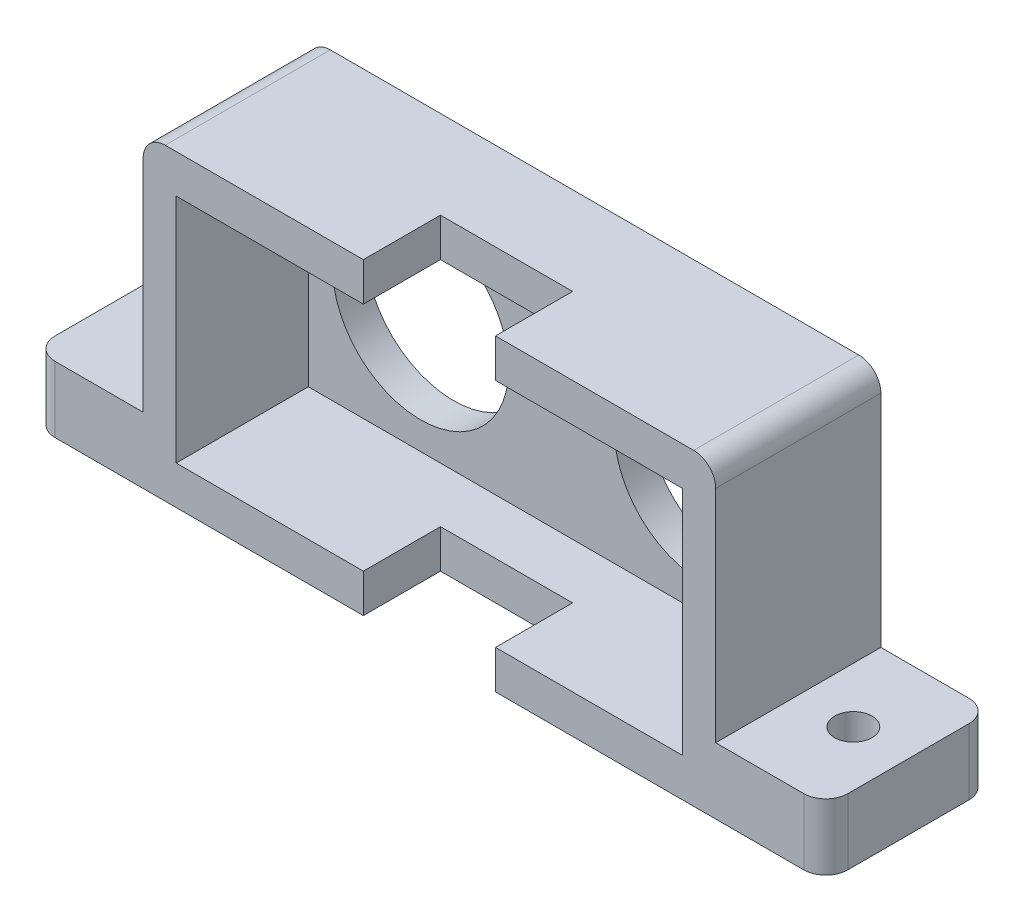
SolidWorks part; units mm, degrees
ref_plane "Plan de face" through (0, 0, 0) normal (0, 0, 1) x (1, 0, 0)
ref_plane "Plan de dessus" through (0, 0, 0) normal (0, 1, 0) x (1, 0, 0)
ref_plane "Plan de droite" through (0, 0, 0) normal (1, 0, 0) x (0, 0, -1)
sketch "Esquisse1" plane through (0, 0, 0) normal (0, 0, 1) x (1, 0, 0)
  line L0 (36, 0) -> (-36, 0)
  line L1 (-36, 0) -> (36, 0) construction
  line L2 (-36, 0) -> (-36, 28) construction
  line L3 (-36, 28) -> (36, 28) construction
  line L4 (36, 0) -> (36, 28) construction
  line L5 (-36, 0) -> (-36, 6)
  line L6 (-36, 6) -> (-26, 6)
  line L7 (-26, 6) -> (-26, 28)
  line L8 (-26, 28) -> (26, 28)
  line L9 (26, 28) -> (26, 6)
  line L10 (26, 6) -> (36, 6)
  line L11 (36, 6) -> (36, 0)
  point P4 (0, 0)
  dimension "D1" = 72
  dimension "D2" = 28
  dimension "D3" = 10
  dimension "D4" = 6
  dimension "D5" = 6
  dimension "D6" = 10
extrude "Boss.-Extru.1" add sketch "Esquisse1" along normal blind 15
sketch "Esquisse2" plane through (0, 0, 15) normal (0, 0, 1) x (1, 0, 0)
  line L0 (0, 0) -> (0, 28) construction
  line L1 (-23, 24.5) -> (23, 24.5) construction
  line L2 (-23, 24.5) -> (-23, 3.5) construction
  line L3 (-23, 3.5) -> (23, 3.5) construction
  line L4 (23, 24.5) -> (23, 3.5) construction
  line L5 (26, 28) -> (-26, 28) construction
  line L6 (-23, 14) -> (23, 14) construction
  line L9 (-23, 24.5) -> (23, 24.5)
  line L10 (-23, 24.5) -> (-23, 3.5)
  line L11 (-23, 3.5) -> (23, 3.5)
  line L12 (23, 24.5) -> (23, 3.5)
  point P4 (0, 3.5)
  point P9 (0, 14)
  dimension "D1" = 46
  dimension "D2" = 21
extrude "Enlèv. mat.-Extru.1" cut sketch "Esquisse2" against normal offset from surface (12 mm away) 3 up to face at (0, 10, 0)
sketch "Esquisse4" plane through (0, 0, 3) normal (0, 0, 1) x (1, 0, 0)
  line L0 (-4.8, 14) -> (4.8, 14) construction
  line L1 (0, 0) -> (0, 28) construction
  line L2 (-36, 0) -> (36, 0) construction
  line L3 (26, 28) -> (-26, 28) construction
  circle A0 centre (-12.8, 14) radius 8
  circle A1 centre (12.8, 14) radius 8
  point P12 (0, 14)
  point P13 (0, 14)
  dimension "D1" = 16
  dimension "D2" = 16
  dimension "D3" = 9.6
extrude "Enlèv. mat.-Extru.2" cut sketch "Esquisse4" against normal blind 3
sketch "Esquisse5" plane through (0, 0, 0) normal (0, -1, 0) x (1, 0, 0)
  line L0 (-36, 15) -> (36, 15) construction
  line L1 (-6, 15) -> (6, 15)
  line L2 (-6, 15) -> (-6, 8)
  line L3 (-6, 8) -> (6, 8)
  line L4 (6, 15) -> (6, 8)
  line L5 (0, 0) -> (0, 15) construction
  point P9 (0, 15)
  dimension "D1" = 12
  dimension "D2" = 7
extrude "Enlèv. mat.-Extru.3" cut sketch "Esquisse5" against normal up to surface (28 mm away) up to face at (0, 28, 7.5)
fillet "Congé1" radius 2 6 edges at (-36, 3, 0) (36, 3, 0) (36, 3, 15) (-36, 3, 15) (-26, 28, 7.5) (26, 28, 7.5)
sketch "Esquisse6" plane through (0, 6, 0) normal (0, 1, 0) x (1, 0, 0)
  line L0 (-36, -7.5) -> (36, -7.5) construction
  line L1 (-36, -13) -> (-36, -2) construction
  line L2 (36, -13) -> (36, -2) construction
  circle A0 centre (31, -7.5) radius 1
  circle A1 centre (-31, -7.5) radius 1
  dimension "D1" = 2
  dimension "D2" = 2
  dimension "D3" = 5
  dimension "D4" = 5
hole_wizard "Dégagement M31" positions "Esquisse7" profile "Esquisse9" hole size "M3" standard "ISO" end condition through all
sketch "Esquisse7" plane through (0, 6, 0) normal (0, 1, 0) x (1, 0, 0)
  point P0 (-31, -7.5)
  point P3 (31, -7.5)
sketch "Esquisse9" plane through (-31, 6, 7.5) normal (1, 0, 0) x (0, 0, 1)
  line L0 (0, 0) -> (0, 6)
  line L1 (0, 6) -> (1.7, 6)
  line L2 (1.7, 6) -> (1.7, 0)
  line L5 (1.7, 0) -> (0, 0)
  line L11 (0, -6.35) -> (0, 107.95) construction
  dimension "Diamètre du perçage jusqu'au prochain" = 3.4
  dimension "Profondeur du perçage jusqu'au prochain" = 6
